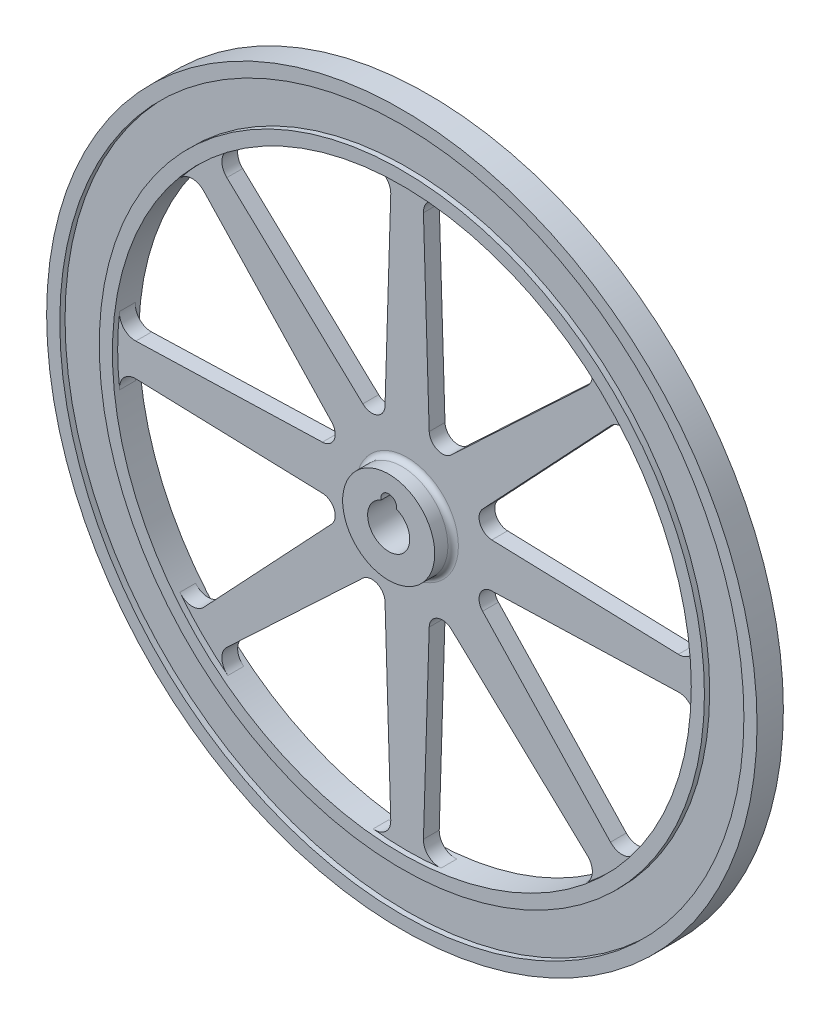
SolidWorks part; units mm, degrees
ref_plane "Front Plane" through (0, 0, 0) normal (0, 0, 1) x (1, 0, 0)
ref_plane "Top Plane" through (0, 0, 0) normal (0, 1, 0) x (1, 0, 0)
ref_plane "Right Plane" through (0, 0, 0) normal (1, 0, 0) x (0, 0, -1)
sketch "Sketch1" plane through (0, 0, 0) normal (0, 0, 1) x (1, 0, 0)
  line L0 (0, 176.4865) -> (0, -179.4413) construction
  line L1 (-203.4784, 0) -> (199.521, 0) construction
  line L2 (6, 109.8362) -> (8.3963, 32.1816)
  line L3 (-8.3963, 32.1816) -> (-6, 109.8362)
  line L4 (-73.4233, 81.9086) -> (-16.8187, 28.6929)
  line L5 (16.8187, 28.6929) -> (73.4233, 81.9086)
  line L6 (0, 0) -> (-144.8317, 144.8317) construction
  line L7 (81.9086, 73.4233) -> (28.6929, 16.8187)
  line L8 (32.1816, 8.3963) -> (109.8362, 6)
  line L9 (109.8362, -6) -> (32.1816, -8.3963)
  line L10 (28.6929, -16.8187) -> (81.9086, -73.4233)
  line L11 (73.4233, -81.9086) -> (16.8187, -28.6929)
  line L12 (8.3963, -32.1816) -> (6, -109.8362)
  line L13 (-6, -109.8362) -> (-8.3963, -32.1816)
  line L14 (-16.8187, -28.6929) -> (-73.4233, -81.9086)
  line L15 (-81.9086, -73.4233) -> (-28.6929, -16.8187)
  line L16 (-32.1816, -8.3963) -> (-109.8362, -6)
  line L17 (-109.8362, 6) -> (-32.1816, 8.3963)
  line L18 (-28.6929, 16.8187) -> (-81.9086, 73.4233)
  circle A0 centre (0, 0) radius 135
  circle A1 centre (0, 0) radius 130
  circle A2 centre (0, 0) radius 115
  circle A3 centre (0, 0) radius 110
  circle A4 centre (0, 0) radius 8
  circle A5 centre (0, 0) radius 17.5
  circle A6 centre (0, 0) radius 35 construction
  arc A8 (-16.8187, 28.6929) -> (-8.3963, 32.1816) centre (-13.3939, 32.3358) ccw
  arc A9 (8.3963, 32.1816) -> (16.8187, 28.6929) centre (13.3939, 32.3358) ccw
  arc A10 (28.6929, 16.8187) -> (32.1816, 8.3963) centre (32.3358, 13.3939) ccw
  arc A11 (32.1816, -8.3963) -> (28.6929, -16.8187) centre (32.3358, -13.3939) ccw
  arc A12 (16.8187, -28.6929) -> (8.3963, -32.1816) centre (13.3939, -32.3358) ccw
  arc A13 (-8.3963, -32.1816) -> (-16.8187, -28.6929) centre (-13.3939, -32.3358) ccw
  arc A14 (-28.6929, -16.8187) -> (-32.1816, -8.3963) centre (-32.3358, -13.3939) ccw
  arc A15 (-32.1816, 8.3963) -> (-28.6929, 16.8187) centre (-32.3358, 13.3939) ccw
  arc A16 (2.9468, 7.4375) -> (-2.9468, 7.4375) centre (0, 8) ccw
  point P12 (0, 0)
  point P21 (0, 35)
  point P48 (0, 0)
  point P62 (0, 0)
  point P87 (0, 0)
  dimension "D1" = 270
  dimension "D2" = 260
  dimension "D3" = 230
  dimension "D4" = 220
  dimension "D5" = 16
  dimension "D6" = 35
  dimension "D7" = 70
  dimension "D8" = 6
  dimension "D11" = 5
  dimension "D12" = 22.5
  dimension "D13" = 6
  dimension "D10" = 6
  dimension "D14" = 8
  dimension "D9" = 45
extrude "Boss-Extrude1" add sketch "Sketch1" along normal mid plane 20 contours A5 A16 A4 region at (-17.005, 0, 0)
extrude "Boss-Extrude3" add sketch "Sketch1<4>" along normal mid plane 6 contours A15 L17 A3 L16 A14 L15 L14 A13 L13 L12 A12 L11 L10 A11 L9 L8 A10 L7 L5 A9 L2 L3 A8 L4 L18 A5 | A1 A2 region at (4.0884, 70.9129, 0) region at (-126.323, 0, 0)
sketch "Sketch1<4>" plane through (0, 0, 0) normal (0, 0, 1) x (1, 0, 0) same geometry as "Sketch1"
extrude "Boss-Extrude4" add sketch "Sketch1<5>" along normal mid plane 10 contours A2 A3 | A0 A1 region at (-131.1816, 0, 0) region at (-111.7473, 0, 0)
sketch "Sketch1<5>" plane through (0, 0, 0) normal (0, 0, 1) x (1, 0, 0) same geometry as "Sketch1"
fillet "Fillet1" radius 6 16 edges at (-73.4233, 81.9086, 0) (-81.9086, 73.4233, 0) (-109.8362, -6, 0) (-109.8362, 6, 0) (-81.9086, -73.4233, 0) (-73.4233, -81.9086, 0) (-6, -109.8362, 0) (6, -109.8362, 0) (81.9086, -73.4233, 0) (73.4233, -81.9086, 0) (109.8362, 6, 0) (109.8362, -6, 0) (73.4233, 81.9086, 0) (81.9086, 73.4233, 0) (6, 109.8362, 0) (-6, 109.8362, 0)
fillet "Fillet2" radius 2 2 edges at (17.5, 0, 3) (17.5, 0, -3)
